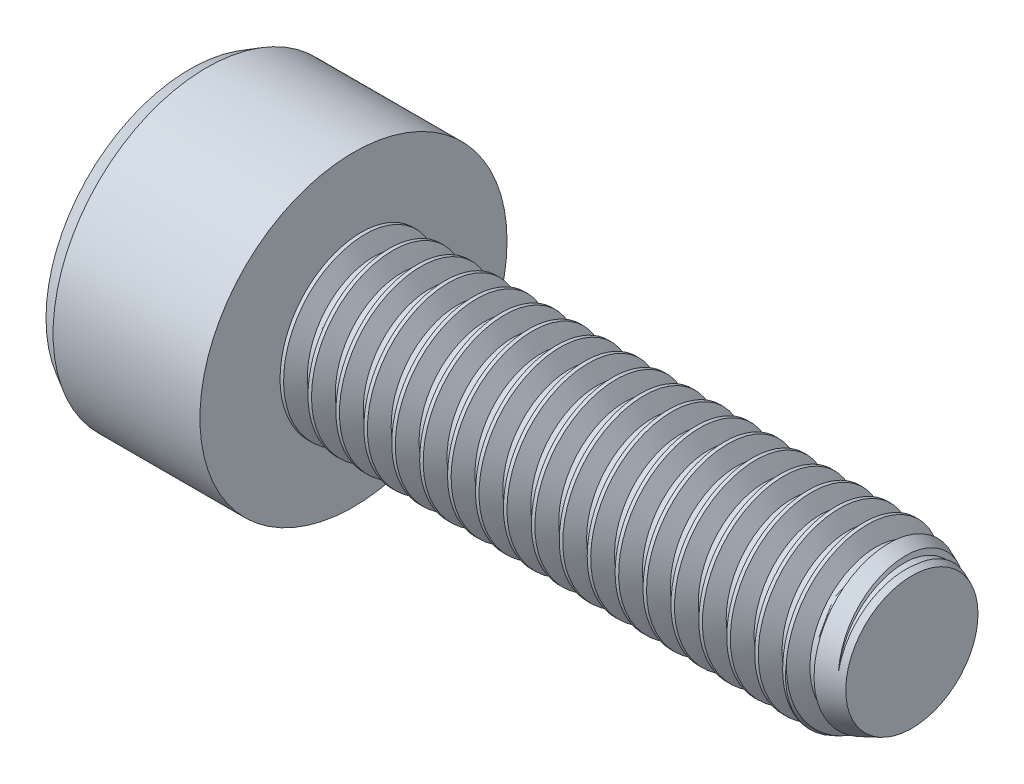
SolidWorks part; units mm, degrees
ref_plane "Front Plane" through (0, 0, 0) normal (0, 0, 1) x (1, 0, 0)
ref_plane "Top Plane" through (0, 0, 0) normal (0, 1, 0) x (1, 0, 0)
ref_plane "Right Plane" through (0, 0, 0) normal (1, 0, 0) x (0, 0, -1)
sketch "Sketch1" plane through (0, 0, 0) normal (0, 0, 1) x (1, 0, 0)
  line L0 (0, 4.2708) -> (0, -3.2523) construction
  line L1 (10, 4.2708) -> (10, -3.2523) construction
  line L2 (0, 0) -> (10, 0) construction
  dimension "LENGTH" = 10
sketch "Sketch2" plane through (0, 0, 0) normal (1, 0, 0) x (0, 0, -1)
  circle A0 centre (0, 0) radius 1.5
  dimension "D1" = 3
extrude "Boss-Extrude1" add sketch "Sketch2" along normal up to vertex (10 mm away) up to point (10, 0, 0)
chamfer "Chamfer1" distance 0.762 angle 22.5 1 edges at (10, 0, -1.5) first distance on face at (10, 0, -1.5)
thread "Thread1" pitch 0.5 method cut profile "Thread Profile1" start angle 0, offset 1, length 0, pitch 0.5, diameter 3
ref_plane "Plane1" through (-1, 0, -1.5) normal (0, -1, 0) x (0, 0, -1)
sketch "Thread Profile1" plane through (-1, 0, -1.5) normal (0, -1, 0) x (0, 0, -1)
  line L0 (0, 0) -> (0, 0.5) construction
  line L11 (0, 0) -> (0, 0.4375)
  line L12 (0, 0.4375) -> (-0.2706, 0.2812)
  line L13 (-0.2706, 0.2812) -> (-0.2706, 0.1562)
  line L15 (-0.2706, 0.1562) -> (0, 0)
  line L17 (-0.2706, 0.2187) -> (0, 0.2187) construction
  point P2 (0, 0)
  dimension "Pitch" = 0.5
  dimension "Profile_Angle" = 60
  dimension "Profile_Land" = 0.125
  dimension "Profile_Height" = 0.2706
sketch "Sketch5" plane through (0, 0, 0) normal (-1, 0, 0) x (0, 0, 1)
  circle A0 centre (0, 0) radius 2.75
  dimension "D1" = 5.5
extrude "Boss-Extrude2" add sketch "Sketch5" along normal blind 2.93
sketch "Sketch6" plane through (-2.93, 0, 0) normal (-1, 0, 0) x (0, 0, 1)
  line L1 (-0.7217, 1.25) -> (-1.4434, 0)
  line L2 (-1.4434, 0) -> (-0.7217, -1.25)
  line L3 (-0.7217, -1.25) -> (0.7217, -1.25)
  line L4 (0.7217, -1.25) -> (1.4434, 0)
  line L5 (1.4434, 0) -> (0.7217, 1.25)
  line L6 (0.7217, 1.25) -> (-0.7217, 1.25)
  circle A0 centre (0, 0) radius 1.25 construction
  dimension "D1" = 2.5
extrude "Cut-Extrude1" cut sketch "Sketch6" against normal blind 1.3
chamfer "Chamfer2" distance 0.3 angle 30 1 edges at (-2.93, 0, 2.75) first distance on face at (-2.93, 0, 2.75)
